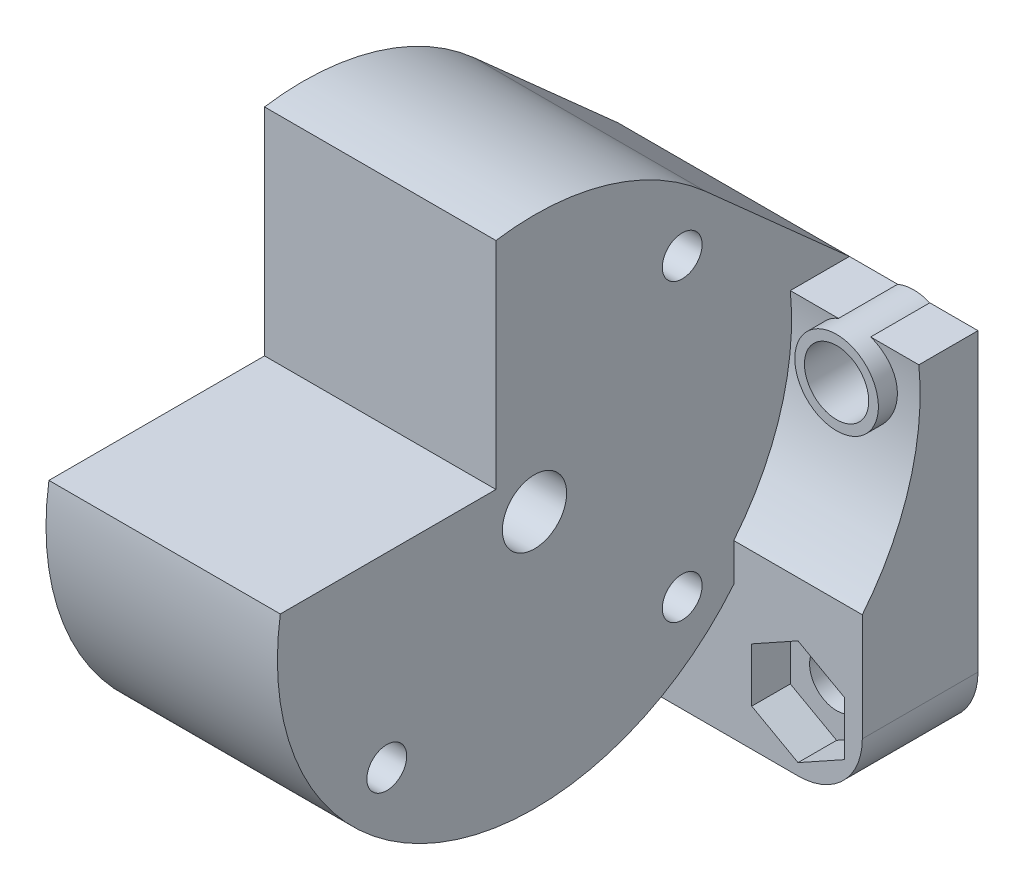
SolidWorks part; units mm, degrees
ref_plane "Front Plane" through (0, 0, 0) normal (0, 0, 1) x (1, 0, 0)
ref_plane "Top Plane" through (0, 0, 0) normal (0, 1, 0) x (1, 0, 0)
ref_plane "Right Plane" through (0, 0, 0) normal (1, 0, 0) x (0, 0, -1)
sketch "Sketch2" plane through (0, 0, 0) normal (0, 0, 1) x (1, 0, 0)
  line L0 (18.8275, -105.2918) -> (18.8275, -140.2918)
  line L1 (18.8275, -140.2918) -> (-31.1725, -140.2918)
  line L2 (-31.1725, -140.2918) -> (18.8275, -105.2918)
  circle A0 centre (-11.1725, -135.2918) radius 2.1
  circle A1 centre (13.8275, -135.2918) radius 2.1
  circle A2 centre (13.8275, -115.2918) radius 2.1
extrude "Boss-Extrude2" add sketch "Sketch2" along normal blind 4.5
sketch "Sketch3" plane through (18.8275, 0, 0) normal (1, 0, 0) x (0, 0, -1)
  line L0 (-2.3606, -114.2918) -> (-24.5, -114.2918) construction
  line L2 (-4.5, -105.2918) -> (0, -105.2918) construction
  line L3 (-24.5, -114.2918) -> (-38.6421, -128.4339) construction
  line L4 (-24.5, -114.2918) -> (-38.6421, -100.1497) construction
  line L5 (-38.6421, -100.1497) -> (-10.3579, -128.4339) construction
  line L6 (-38.6421, -128.4339) -> (-10.3579, -100.1497) construction
  line L7 (-4.5, -105.2918) -> (-4.5, -123.2918)
  line L8 (-4.5, -123.2918) -> (-6.6394, -123.2918)
  line L10 (-4.5, -105.2918) -> (-6.6394, -105.2918)
  line L12 (-4.5, -114.2918) -> (-6.6394, -105.2918) construction
  line L13 (-4.5, -114.2918) -> (-6.6394, -123.2918) construction
  circle A0 centre (-24.5, -114.2918) radius 20
  circle A1 centre (-24.5, -114.2918) radius 16
  circle A2 centre (-35.8137, -125.6055) radius 1.55
  circle A3 centre (-35.8137, -102.9781) radius 1.55
  circle A4 centre (-13.1863, -102.9781) radius 1.55
  circle A5 centre (-13.1863, -125.6055) radius 1.55
  circle A6 centre (-24.5, -114.2918) radius 2.5
  point P21 (-4.5, -114.2918)
  line M6 (-4.5, -105.2918) -> (-4.5, -140.2918)
  dimension "D3" = 40
  dimension "D4" = 32
  dimension "D5" = 3.1
  dimension "D6" = 16
  dimension "D7" = 3.1
  dimension "D8" = 3.1
  dimension "D9" = 3.1
  dimension "D10" = 16
  dimension "D11" = 16
  dimension "D12" = 16
  dimension "D13" = 5
  dimension "D2" = 9
extrude "Boss-Extrude7" add sketch "Sketch3" against normal blind 8 contours A5 A1 A4 A3 A2 A6 | A0 A5 A1 A2 A3 A4 | A0 L10 M6 | A0 L8 L7 region at (18.8275, -107.517, 5.1355) region at (18.8275, -118.7864, 5.5926) region at (18.8275, -121.0666, 5.1355) region at (18.8275, -119.5388, 9.8647)
chamfer "Chamfer1" distance 2 angle 45 4 edges at (10.8275, -102.9781, 34.2637) (10.8275, -102.9781, 11.6363) (10.8275, -125.6055, 11.6363) (10.8275, -125.6055, 34.2637)
sketch "Sketch7" plane through (0, 0, 4.5) normal (0, 0, 1) x (1, 0, 0)
  line L0 (-12.4325, -127.1738) -> (-31.1725, -140.2918)
  line L1 (10.8275, -110.8918) -> (-31.1725, -140.2918) construction
  line L2 (-31.1725, -140.2918) -> (-16.5913, -140.2918)
  line L3 (-31.1725, -140.2918) -> (18.8275, -140.2918) construction
  circle A0 centre (-11.1725, -135.2918) radius 7.3731
extrude "Cut-Extrude4" cut sketch "Sketch7" against normal blind 8 contours A0 L0 region at (-22.3391, -137.2316, 4.5)
fillet "Fillet1" radius 5 1 edges at (18.8275, -140.2918, 2.25)
fillet "Fillet2" radius 5 1 edges at (-16.5913, -140.2918, 2.25)
sketch "Sketch8" plane through (0, 0, 0) normal (0, 0, -1) x (-1, 0, 0)
  circle A0 centre (-13.8275, -115.2918) radius 2.5
  dimension "D1" = 5
extrude "Cut-Extrude5" cut sketch "Sketch8" against normal blind 7
sketch "Sketch9" plane through (18.8275, 0, 0) normal (1, 0, 0) x (0, 0, -1)
  line L0 (-4.5, -114.2918) -> (-4.5, -105.2918)
  line L1 (-4.5, -105.2918) -> (-6.6394, -105.2918)
  circle A0 centre (-24.5, -114.2918) radius 20
  line M6 (-4.5, -105.2918) -> (-6.6394, -105.2918)
extrude "Cut-Extrude6" cut sketch "Sketch9" against normal blind 14 contours A0 L0 M6 region at (18.8275, -107.517, 5.1355)
sketch "Sketch10" plane through (0, 0, 4.5) normal (0, 0, 1) x (1, 0, 0)
  line L0 (18.8275, -105.2918) -> (10.8275, -110.8918)
  line L1 (18.8275, -105.2918) -> (-15.4007, -129.2515) construction
  line L2 (10.8275, -114.2918) -> (10.8275, -123.2918) construction
  line L3 (18.8275, -105.2918) -> (18.8275, -114.2918)
  line L4 (18.8275, -114.2918) -> (10.8275, -114.2918)
  line L5 (10.8275, -114.2918) -> (10.8275, -110.8918)
  dimension "D1" = 0
extrude "Boss-Extrude9" add sketch "Sketch10" along normal blind 3
sketch "Sketch11" plane through (0, 0, 0) normal (0, 0, -1) x (-1, 0, 0)
  circle A0 centre (-13.8275, -115.2918) radius 2.5
extrude "Cut-Extrude7" cut sketch "Sketch11" against normal blind 7
sketch "Sketch12" plane through (0, 0, 4.5) normal (0, 0, 1) x (1, 0, 0)
  line L0 (10.8275, -110.8918) -> (10.8275, -123.2918)
  line L1 (10.8275, -123.2918) -> (18.8275, -123.2918)
  line L2 (18.8275, -123.2918) -> (18.8275, -135.2918)
  line L3 (10.8275, -110.8918) -> (-15.4007, -129.2515)
  line L4 (-13.5456, -140.2918) -> (13.8275, -140.2918)
  arc A0 (13.8275, -140.2918) -> (18.8275, -135.2918) centre (13.8275, -135.2918) ccw
  arc A1 (-13.5456, -140.2918) -> (-18.5456, -135.2918) centre (-13.5456, -135.2918) cw
  arc A2 (-15.4007, -129.2515) -> (-18.5456, -135.2918) centre (-11.1725, -135.2918) ccw
  circle A3 centre (-11.1725, -135.2918) radius 2.1
  circle A4 centre (13.8275, -135.2918) radius 2.1
extrude "Boss-Extrude12" add sketch "Sketch12" along normal blind 4.5
sketch "Sketch14" plane through (0, 0, 9) normal (0, 0, 1) x (1, 0, 0)
  line L0 (-11.1725, -133.1918) -> (-11.1725, -131.1918) construction
  line L2 (-14.7725, -137.3918) -> (-14.7725, -133.1918)
  line L4 (-7.5725, -137.3918) -> (-7.5725, -133.1918)
  line L5 (-14.7725, -137.3918) -> (-7.5725, -133.1918) construction
  line L6 (-14.7725, -133.1918) -> (-7.5725, -137.3918) construction
  line L7 (-14.7725, -135.2918) -> (-7.5725, -135.2918) construction
  line L8 (-11.1725, -137.3918) -> (-11.1725, -139.3918) construction
  line L9 (-11.1725, -131.1918) -> (-14.7725, -133.1918)
  line L10 (-11.1725, -131.1918) -> (-7.5725, -133.1918)
  line L11 (-14.7725, -137.3918) -> (-11.1725, -139.3918)
  line L12 (-11.1725, -139.3918) -> (-7.5725, -137.3918)
  line L13 (-11.1725, -135.2918) -> (13.8275, -135.2918) construction
  line L14 (1.3275, -135.2918) -> (1.3275, -132.5939) construction
  line L15 (10.2275, -137.3918) -> (10.2275, -133.1918)
  line L16 (13.8275, -139.3918) -> (10.2275, -137.3918)
  line L17 (17.4275, -137.3918) -> (13.8275, -139.3918)
  line L18 (17.4275, -137.3918) -> (17.4275, -133.1918)
  line L19 (13.8275, -131.1918) -> (17.4275, -133.1918)
  line L20 (13.8275, -131.1918) -> (10.2275, -133.1918)
  point P0 (-11.1725, -135.2918)
  dimension "D1" = 7.2
  dimension "D2" = 4.2
  dimension "D3" = 2
extrude "Cut-Extrude8" cut sketch "Sketch14" against normal blind 3
sketch "Sketch16" plane through (18.8275, 0, 0) normal (1, 0, 0) x (0, 0, -1)
  circle A0 centre (-24.5, -114.2918) radius 20
extrude "Cut-Extrude9" cut sketch "Sketch16" against normal blind 6
sketch "Sketch17" plane through (10.8275, 0, 0) normal (-1, 0, 0) x (0, 0, 1)
  circle A0 centre (24.5, -114.2918) radius 20
  circle A1 centre (24.5, -114.2918) radius 2.5
  circle A2 centre (35.8137, -102.9781) radius 1.55
  circle A3 centre (13.1863, -102.9781) radius 1.55
  circle A4 centre (13.1863, -125.6055) radius 1.55
  circle A5 centre (35.8137, -125.6055) radius 1.55
  dimension "D1" = 3.1
  dimension "D2" = 3.1
  dimension "D3" = 3.1
  dimension "D4" = 3.1
extrude "Boss-Extrude16" add sketch "Sketch17" against normal up to surface (2 mm away) contours A1 | A0 up to face at (12.8275, -114.2918, 22)
sketch "Sketch18" plane through (10.8275, 0, 0) normal (-1, 0, 0) x (0, 0, 1)
  circle A0 centre (24.5, -114.2918) radius 20
extrude "Boss-Extrude17" add sketch "Sketch18" along normal blind 6
sketch "Sketch19" plane through (0, 0, 9) normal (0, 0, 1) x (1, 0, 0)
  line L0 (12.8275, -109.4918) -> (18.8275, -105.2918)
  line L1 (18.8275, -105.2918) -> (18.8275, -126.931)
  line L2 (18.8275, -126.931) -> (12.8275, -126.931)
  line L3 (12.8275, -126.931) -> (12.8275, -109.4918)
extrude "Boss-Extrude18" add sketch "Sketch19" against normal blind 6
sketch "Sketch20" plane through (12.8275, 0, 0) normal (1, 0, 0) x (0, 0, -1)
  line L0 (-24.5, -114.2918) -> (-35.8137, -102.9781) construction
  line L1 (-24.5, -114.2918) -> (-13.1863, -102.9781) construction
  line L2 (-24.5, -114.2918) -> (-35.8137, -125.6055) construction
  line L3 (-24.5, -114.2918) -> (-13.1863, -125.6055) construction
  circle A0 centre (-24.5, -114.2918) radius 16
  circle A1 centre (-35.8137, -102.9781) radius 1.55
  circle A2 centre (-13.1863, -102.9781) radius 1.55
  circle A3 centre (-35.8137, -125.6055) radius 1.55
  circle A4 centre (-13.1863, -125.6055) radius 1.55
  circle A5 centre (-24.5, -114.2918) radius 2.5
  circle M5 centre (-24.5, -114.2918) radius 2.5
  dimension "D1" = 32
  dimension "D2" = 3.1
  dimension "D3" = 3.1
  dimension "D4" = 3.1
  dimension "D5" = 3.1
  dimension "D6" = 16
  dimension "D7" = 16
  dimension "D8" = 16
  dimension "D9" = 16
extrude "Cut-Extrude10" cut sketch "Sketch20" against normal blind 15 contours A0 A1 | A0 A1 | A0 A2 | A0 A2 | A0 A3 | A0 A3 | A0 A4 | A0 A4 | M5 region at (12.8275, -103.4527, 13.6609) region at (12.8275, -102.5226, 12.7308) region at (12.8275, -126.061, 12.7308) region at (12.8275, -125.1309, 13.6609) region at (12.8275, -103.4527, 35.3391) region at (12.8275, -102.5226, 36.2692) region at (12.8275, -126.061, 36.2692) region at (12.8275, -125.1309, 35.3391) region at (12.8275, -114.2918, 24.5)
sketch "Sketch22" plane through (0, 0, 0) normal (0, 0, -1) x (-1, 0, 0)
  circle A0 centre (-13.8275, -115.2918) radius 2.5
extrude "Boss-Extrude19" add sketch "Sketch22" against normal up to surface (9 mm away) up to face at (-11.1725, -135.2918, 9)
sketch "Sketch23" plane through (12.8275, 0, 0) normal (1, 0, 0) x (0, 0, -1)
  circle A0 centre (-24.5, -114.2918) radius 20
extrude "Cut-Extrude11" cut sketch "Sketch23" along normal blind 15
sketch "Sketch24" plane through (0, 0, 9) normal (0, 0, 1) x (1, 0, 0)
  line L0 (12.8275, -109.4918) -> (18.8275, -109.4918)
  line L1 (18.8275, -126.931) -> (18.8275, -105.2918) construction
  line L2 (18.8275, -103.8885) -> (12.8275, -109.4918)
  line L3 (18.8275, -103.8885) -> (18.8275, -109.4918)
extrude "Cut-Extrude12" cut sketch "Sketch24" against normal blind 15
chamfer "Chamfer4" distance 2 angle 45 4 edges at (4.8275, -102.9781, 14.7363) (4.8275, -125.6055, 14.7363) (4.8275, -125.6055, 37.3637) (4.8275, -102.9781, 37.3637)
sketch "Sketch25" plane through (4.8275, 0, 0) normal (-1, 0, 0) x (0, 0, 1)
  line L0 (24.5, -114.2918) -> (44.5, -114.2918) construction
  line L1 (24.5, -114.2918) -> (24.5, -94.2918) construction
  line L2 (27.5, -94.5181) -> (27.5, -111.2918)
  line L3 (27.5, -111.2918) -> (44.2737, -111.2918)
  arc A0 (9, -126.931) -> (4.516, -115.0918) centre (24.5, -114.2918) ccw construction
  arc A1 (44.2737, -111.2918) -> (27.5, -94.5181) centre (24.5, -114.2918) ccw
  dimension "D1" = 3
  dimension "D2" = 3
extrude "Cut-Extrude13" cut sketch "Sketch25" against normal blind 15
sketch "Sketch26" plane through (0, 0, 0) normal (0, 0, -1) x (-1, 0, 0)
  line L0 (-13.8275, -135.2918) -> (-13.8275, -115.2918) construction
  circle A0 centre (-13.8275, -115.2918) radius 1.95
  dimension "D2" = 3.9
  dimension "D1" = 20
extrude "Cut-Extrude15" cut sketch "Sketch26" against normal blind 4
sketch "Sketch27" plane through (4.8275, 0, 0) normal (-1, 0, 0) x (0, 0, 1)
  line L0 (27.5, -94.5181) -> (27.5, -111.2918)
  line L1 (27.5, -111.2918) -> (44.2737, -111.2918)
  arc A0 (27.5, -94.5181) -> (44.2737, -111.2918) centre (24.5, -114.2918) ccw
  circle A1 centre (13.1863, -102.9781) radius 1.55
  circle A2 centre (13.1863, -125.6055) radius 1.55
  circle A3 centre (35.8137, -125.6055) radius 1.55
extrude "Boss-Extrude20" add sketch "Sketch27" against normal blind 4
sketch "Sketch28" plane through (8.8275, 0, 0) normal (1, 0, 0) x (0, 0, -1)
  circle A0 centre (-24.5, -114.2918) radius 2.5
extrude "Cut-Extrude16" cut sketch "Sketch28" against normal blind 13
sketch "Sketch29" plane through (12.8275, 0, 0) normal (1, 0, 0) x (0, 0, -1)
  circle A0 centre (-24.5, -114.2918) radius 20
extrude "Cut-Extrude17" cut sketch "Sketch29" against normal blind 4
sketch "Sketch30" plane through (4.8275, 0, 0) normal (-1, 0, 0) x (0, 0, 1)
  line L0 (27.5, -94.5181) -> (27.5, -111.2918)
  line L1 (27.5, -111.2918) -> (44.2737, -111.2918)
  circle A0 centre (24.5, -114.2918) radius 20
  circle A1 centre (13.1863, -102.9781) radius 1.55
  circle A2 centre (13.1863, -125.6055) radius 1.55
  circle A3 centre (35.8137, -125.6055) radius 1.55
  circle A4 centre (24.5, -114.2918) radius 2.5
  circle M1 centre (24.5, -114.2918) radius 2.5
  line M2 (44.2737, -111.2918) -> (27.5, -111.2918)
  line M3 (27.5, -111.2918) -> (27.5, -94.5181)
  arc M4 (27.5, -94.5181) -> (4.516, -115.0918) centre (24.5, -114.2918) ccw
  line M5 (4.516, -115.0918) -> (9, -115.0918)
  line M6 (9, -115.0918) -> (9, -126.931)
  arc M7 (9, -126.931) -> (44.2737, -111.2918) centre (24.5, -114.2918) ccw
  circle M8 centre (35.8137, -125.6055) radius 1.55
  circle M9 centre (13.1863, -125.6055) radius 1.55
  circle M10 centre (13.1863, -102.9781) radius 1.55
extrude "Boss-Extrude21" add sketch "Sketch30" along normal blind 4 contours M7 M2 M3 M4 M5 M6 M9 M10 M8 M1 | A0 M5 M6 region at (4.8275, -102.905, 26.9343) region at (4.8275, -119.5624, 7.2251)
chamfer "Chamfer5" distance 2 angle 45 3 edges at (0.8275, -125.6055, 14.7363) (0.8275, -125.6055, 37.3637) (0.8275, -102.9781, 14.7363)
sketch "Sketch31" plane through (8.8275, 0, 0) normal (1, 0, 0) x (0, 0, -1)
  line L0 (-35.8137, -125.6055) -> (-35.8137, -128.5555) construction
  line L1 (-24.5, -114.2918) -> (-24.5, -117.2418) construction
  line L2 (-13.1863, -125.6055) -> (-13.1863, -128.5555) construction
  line L3 (-13.1863, -102.9781) -> (-13.1863, -105.9281) construction
  circle A4 centre (-24.5, -117.2418) radius 2.5
  circle A5 centre (-35.8137, -128.5555) radius 1.55
  circle A6 centre (-13.1863, -105.9281) radius 1.55
  circle A7 centre (-13.1863, -128.5555) radius 1.55
  dimension "D6" = 5
  dimension "D7" = 3.1
  dimension "D8" = 3.1
  dimension "D9" = 3.1
  dimension "D1" = 2.95
  dimension "D2" = 2.95
  dimension "D3" = 2.95
  dimension "D4" = 2.95
extrude "Cut-Extrude18" cut sketch "Sketch31" against normal blind 14
sketch "Sketch32" plane through (8.8275, 0, 0) normal (1, 0, 0) x (0, 0, -1)
  circle A0 centre (-24.5, -117.2418) radius 2.5
  circle A1 centre (-13.1863, -105.9281) radius 1.55
  circle A2 centre (-13.1863, -128.5555) radius 1.55
  circle A3 centre (-35.8137, -128.5555) radius 1.55
  circle A4 centre (-35.8137, -125.6055) radius 1.55
  circle A5 centre (-24.5, -114.2918) radius 2.5
  circle A6 centre (-13.1863, -125.6055) radius 1.55
  circle A7 centre (-13.1863, -102.9781) radius 1.55
  arc M1 (-35.3374, -127.0805) -> (-36.29, -127.0805) centre (-35.8137, -128.5555) cw
  arc M2 (-36.29, -127.0805) -> (-35.3374, -127.0805) centre (-35.8137, -125.6055) cw
  arc M3 (-12.71, -104.4531) -> (-13.6626, -104.4531) centre (-13.1863, -105.9281) cw
  arc M4 (-13.6626, -104.4531) -> (-12.71, -104.4531) centre (-13.1863, -102.9781) cw
  arc M5 (-12.71, -127.0805) -> (-13.6626, -127.0805) centre (-13.1863, -128.5555) cw
  arc M6 (-13.6626, -127.0805) -> (-12.71, -127.0805) centre (-13.1863, -125.6055) cw
  arc M7 (-22.4815, -115.7668) -> (-26.5185, -115.7668) centre (-24.5, -117.2418) cw
  arc M8 (-26.5185, -115.7668) -> (-22.4815, -115.7668) centre (-24.5, -114.2918) cw
  line M9 (-27.5, -111.2918) -> (-44.2737, -111.2918)
  arc M10 (-44.2737, -111.2918) -> (-9, -126.931) centre (-24.5, -114.2918) ccw
  arc M11 (-9, -126.931) -> (-4.6003, -112.2918) centre (-24.5, -114.2918) ccw
  arc M12 (-4.6003, -112.2918) -> (-27.5, -94.5181) centre (-24.5, -114.2918) ccw
  line M13 (-27.5, -94.5181) -> (-27.5, -111.2918)
extrude "Boss-Extrude22" add sketch "Sketch32" against normal up to surface (8 mm away) contours A1 M4 | A0 M8 | A3 M2 | A2 M6 | M13 M9 M10 M11 M12 M8 M7 M6 M5 M4 M3 M2 M1 region at (8.8275, -113.6746, 24.5) region at (8.8275, -102.9592, 13.1863) region at (8.8275, -125.5866, 13.1863) region at (8.8275, -125.5866, 35.8137) region at (8.8275, -102.905, 26.9343) up to face at (0.8275, -126.0805, 35.8137)
sketch "Sketch33" plane through (8.8275, 0, 0) normal (1, 0, 0) x (0, 0, -1)
  circle A0 centre (-24.5, -117.2418) radius 20
  circle A1 centre (-24.5, -117.2418) radius 2.5
  circle A2 centre (-13.1863, -105.9281) radius 1.55
  circle A3 centre (-13.1863, -128.5555) radius 1.55
  circle A4 centre (-35.8137, -128.5555) radius 1.55
  dimension "D1" = 40
extrude "Boss-Extrude23" add sketch "Sketch33" against normal up to surface (8 mm away) contours A0 | A1 | A2 | A3 | A4 up to face at (0.8275, -128.5555, 37.3637)
sketch "Sketch34" plane through (8.8275, 0, 0) normal (1, 0, 0) x (0, 0, -1)
  arc A0 (-4.5545, -115.7668) -> (-44.4455, -115.7668) centre (-24.5, -114.2918) ccw
  circle A1 centre (-24.5, -117.2418) radius 20
  arc M1 (-27.5, -97.4681) -> (-43.5944, -111.2918) centre (-24.5, -117.2418) ccw
  line M2 (-43.5944, -111.2918) -> (-44.2737, -111.2918)
  arc M3 (-44.2737, -111.2918) -> (-44.4455, -115.7668) centre (-24.5, -114.2918) ccw
  arc M6 (-9, -126.931) -> (-4.6003, -112.2918) centre (-24.5, -114.2918) ccw
  arc M7 (-4.6003, -112.2918) -> (-27.5, -94.5181) centre (-24.5, -114.2918) ccw
  line M8 (-27.5, -94.5181) -> (-27.5, -97.4681)
extrude "Cut-Extrude19" cut sketch "Sketch34" against normal blind 14 contours A0 M8 M2 M1 | A1 M2 M3 | A1 M6 M7 M8 region at (8.8275, -101.3593, 11.8339) region at (8.8275, -100.4169, 35.7378) region at (8.8275, -112.7757, 44.1898)
sketch "Sketch35" plane through (0, 0, 9) normal (0, 0, 1) x (1, 0, 0)
  line L0 (8.8275, -112.2918) -> (18.8275, -112.2918)
  line L1 (12.8275, -109.4918) -> (3.8632, -115.7668) construction
  line L2 (8.8275, -137.2418) -> (8.8275, -97.2418) construction
  line L3 (18.8275, -126.931) -> (18.8275, -109.4918) construction
  line L4 (18.8275, -112.2918) -> (18.8275, -109.4918)
  line L5 (18.8275, -109.4918) -> (8.8275, -109.4918)
  line L6 (8.8275, -109.4918) -> (8.8275, -112.2918)
extrude "Cut-Extrude20" cut sketch "Sketch35" against normal blind 14
sketch "Sketch36" plane through (0.8275, 0, 0) normal (-1, 0, 0) x (0, 0, 1)
  line L2 (27.5, -97.4681) -> (27.5, -114.2418)
  line L3 (27.5, -114.2418) -> (44.2737, -114.2418)
  arc A0 (9, -129.881) -> (4.5106, -117.8918) centre (24.5, -117.2418) ccw construction
  arc A1 (44.2737, -114.2418) -> (27.5, -97.4681) centre (24.5, -117.2418) ccw
extrude "Cut-Extrude21" cut sketch "Sketch36" against normal blind 14
sketch "Sketch37" plane through (0, 0, 0) normal (0, 0, -1) x (-1, 0, 0)
  circle A0 centre (-13.8275, -115.2918) radius 2.5
  dimension "D1" = 5
extrude "Cut-Extrude22" cut sketch "Sketch37" against normal blind 6
sketch "Sketch38" plane through (0, 0, 0) normal (0, 0, -1) x (-1, 0, 0)
  circle A0 centre (-13.8275, -115.2918) radius 3.25
  circle A1 centre (-13.8275, -115.2918) radius 2.5
  dimension "D1" = 6.5
extrude "Boss-Extrude24" add sketch "Sketch38" against normal blind 6
sketch "Sketch40" plane through (8.8275, 0, 0) normal (1, 0, 0) x (0, 0, -1)
  circle A0 centre (-35.8137, -128.5555) radius 1.55
  circle A1 centre (-13.1863, -128.5555) radius 1.55
  circle A2 centre (-13.1863, -105.9281) radius 1.55
extrude "Boss-Extrude25" add sketch "Sketch40" against normal up to surface (8 mm away) up to face at (0.8275, -116.615, 20.4942)
sketch "Sketch41" plane through (8.8275, 0, 0) normal (1, 0, 0) x (0, 0, -1)
  line L0 (-24.5, -117.2418) -> (-13.0095, -105.7513) construction
  line L1 (-24.5, -117.2418) -> (-35.9905, -128.7323) construction
  line L2 (-24.5, -117.2418) -> (-13.0095, -128.7323) construction
  circle A0 centre (-24.5, -117.2418) radius 16.25
  circle A1 centre (-13.0095, -105.7513) radius 1.55
  circle A2 centre (-13.0095, -128.7323) radius 1.55
  circle A3 centre (-35.9905, -128.7323) radius 1.55
  dimension "D1" = 32.5
  dimension "D2" = 3.1
  dimension "D3" = 3.1
  dimension "D4" = 3.1
  dimension "D5" = 16.25
  dimension "D6" = 16.25
  dimension "D7" = 16.25
extrude "Cut-Extrude23" cut sketch "Sketch41" against normal blind 8 contours A0 A1 | A0 A1 | A0 A2 | A0 A2 | A0 A3 | A0 A3 region at (8.8275, -106.2258, 13.484) region at (8.8275, -105.2957, 12.5539) region at (8.8275, -129.1879, 12.5539) region at (8.8275, -128.2578, 13.484) region at (8.8275, -128.2578, 35.516) region at (8.8275, -129.1879, 36.4461)
chamfer "Chamfer7" distance 2 angle 45 3 edges at (0.8275, -128.7323, 11.4595) (0.8275, -128.7323, 34.4405) (0.8275, -105.7513, 11.4595)
sketch "Sketch42" plane through (0.8275, 0, 0) normal (-1, 0, 0) x (0, 0, 1)
  circle A0 centre (24.5, -117.2418) radius 20
extrude "Boss-Extrude26" add sketch "Sketch42" along normal blind 10
sketch "Sketch43" plane through (-9.1725, 0, 0) normal (-1, 0, 0) x (0, 0, 1)
  line L0 (24.5, -117.2418) -> (13.0095, -105.7513) construction
  line L2 (24.5, -117.2418) -> (13.0095, -128.7323) construction
  line L3 (24.5, -117.2418) -> (35.9905, -128.7323) construction
  circle A0 centre (24.5, -117.2418) radius 16.25
  circle A2 centre (13.0095, -105.7513) radius 1.55
  circle A3 centre (13.0095, -128.7323) radius 1.55
  circle A4 centre (35.9905, -128.7323) radius 1.55
  circle A5 centre (24.5, -117.2418) radius 2.5
  dimension "D1" = 32.5
  dimension "D2" = 5
  dimension "D3" = 3.1
  dimension "D4" = 3.1
  dimension "D5" = 3.1
  dimension "D6" = 16.25
  dimension "D7" = 16.25
  dimension "D8" = 16.25
extrude "Cut-Extrude25" cut sketch "Sketch43" against normal blind 30 contours A0 A4 | A0 A4 | A0 A3 | A0 A3 | A0 A2 | A0 A2 | A5 region at (-9.1725, -106.2258, 13.484) region at (-9.1725, -105.2957, 12.5539) region at (-9.1725, -129.1879, 36.4461) region at (-9.1725, -128.2578, 35.516) region at (-9.1725, -128.2578, 13.484) region at (-9.1725, -129.1879, 12.5539) region at (-9.1725, -117.2418, 24.5)
chamfer "Chamfer8" distance 2 angle 45 3 edges at (-9.1725, -128.7323, 14.5595) (-9.1725, -128.7323, 37.5405) (-9.1725, -105.7513, 14.5595)
sketch "Sketch44" plane through (-9.1725, 0, 0) normal (-1, 0, 0) x (0, 0, 1)
  circle A0 centre (13.0095, -105.7513) radius 3.55
  circle A1 centre (35.9905, -128.7323) radius 3.55
  circle A2 centre (13.0095, -128.7323) radius 3.55
extrude "Cut-Extrude26" cut sketch "Sketch44" against normal up to surface (10 mm away) up to face at (0.8275, -107.7321, 34.0097)
sketch "Sketch45" plane through (0, -112.2918, 0) normal (0, 1, 0) x (1, 0, 0)
  line L1 (8.8275, -4.6003) -> (-9.0725, -4.6003)
  line L2 (8.8275, -4.6003) -> (8.8275, 0)
  line L3 (8.8275, 0) -> (-9.0725, 0)
  line L4 (-9.0725, -4.6003) -> (-9.0725, 0)
extrude "Boss-Extrude27" add sketch "Sketch45" against normal blind 15
sketch "Sketch47" plane through (-9.1725, 0, 0) normal (-1, 0, 0) x (0, 0, 1)
  line L0 (9, -124.8918) -> (6.0209, -124.8918) construction
  line L1 (0, -112.2918) -> (7.5104, -112.2918)
  line L2 (0, -112.2918) -> (0, -124.8918)
  line L3 (0, -124.8918) -> (7.5104, -124.8918)
  line L4 (7.5104, -112.2918) -> (7.5104, -124.8918)
extrude "Boss-Extrude29" add sketch "Sketch47" against normal up to surface (18 mm away) up to face at (8.8275, -117.0408, 18.1681)
sketch "Sketch48" plane through (0.8275, 0, 0) normal (1, 0, 0) x (0, 0, -1)
  line L0 (-27.5, -97.4681) -> (-27.5, -114.2418)
  line L1 (-27.5, -114.2418) -> (-44.2737, -114.2418)
  arc A0 (-27.5, -97.4681) -> (-44.2737, -114.2418) centre (-24.5, -117.2418) ccw
extrude "Cut-Extrude27" cut sketch "Sketch48" against normal blind 15
sketch "Sketch49" plane through (-9.1725, 0, 0) normal (-1, 0, 0) x (0, 0, 1)
  line L0 (5.1222, -112.2918) -> (0, -112.2918)
  line L1 (0, -112.2918) -> (11.1894, -102.3144)
  circle A0 centre (24.5, -117.2418) radius 20
  arc M3 (27.5, -97.4681) -> (5.1222, -112.2918) centre (24.5, -117.2418) ccw
  line M4 (5.1222, -112.2918) -> (0, -112.2918)
extrude "Boss-Extrude30" add sketch "Sketch49" against normal up to surface (18 mm away) contours L1 M4 M3 region at (-9.1725, -109.6364, 4.5574) up to face at (8.8275, -116.7052, 18.3794)
